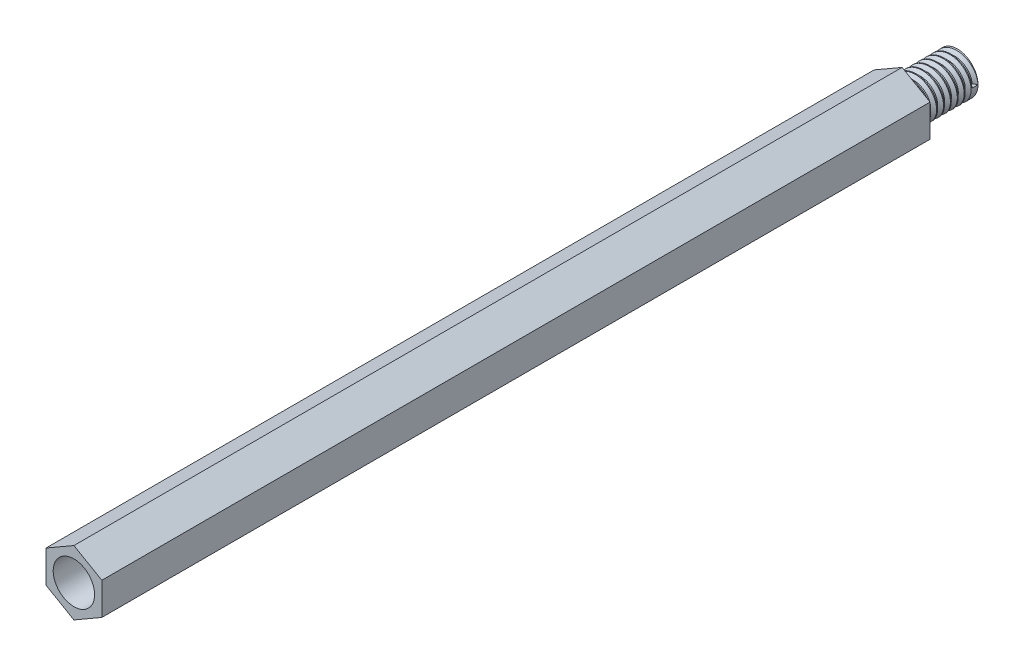
SolidWorks part; units mm, degrees
ref_plane "前视基准面" through (0, 0, 0) normal (0, 0, 1) x (1, 0, 0)
ref_plane "上视基准面" through (0, 0, 0) normal (0, 1, 0) x (1, 0, 0)
ref_plane "右视基准面" through (0, 0, 0) normal (1, 0, 0) x (0, 0, -1)
other "Configuration Table"
sketch "草图1" plane through (0, 0, 0) normal (0, 0, 1) x (1, 0, 0)
  circle A0 centre (0, 0) radius 1.5
  circle A1 centre (0, 0) radius 2.335
  dimension "D1" = 3
  dimension "D2" = 4.67
extrude "凸台-拉伸1" add sketch "草图1" along normal blind 60
sketch "草图3" plane through (0, 0, 0) normal (0, 0, 1) x (1, 0, 0)
  line L1 (0, 2.335) -> (-2.0222, 1.1675)
  line L2 (-2.0222, 1.1675) -> (-2.0222, -1.1675)
  line L3 (-2.0222, -1.1675) -> (0, -2.335)
  line L4 (0, -2.335) -> (2.0222, -1.1675)
  line L5 (2.0222, -1.1675) -> (2.0222, 1.1675)
  line L6 (2.0222, 1.1675) -> (0, 2.335)
  circle A0 centre (0, 0) radius 2.0222 construction
extrude "切除-拉伸2" cut sketch "草图3" along normal blind 60 flip side to cut
sketch "草图4" plane through (0, 0, 0) normal (0, 0, 1) x (1, 0, 0)
  circle A0 centre (0, 0) radius 1.5
sketch "草图5" plane through (0, 0, 0) normal (0, 0, 1) x (1, 0, 0)
  circle A0 centre (0, 0) radius 1.5
extrude "凸台-拉伸2" add sketch "草图5" against normal blind 4 separate body
thread "螺纹线1" pitch 0.5 method cut profile "螺纹线轮廓1" start angle 0, offset 0, length 4, pitch 0.5, diameter 3
ref_plane "基准面1" through (1.5, 0, -4) normal (0, -1, 0) x (1, 0, 0)
sketch "螺纹线轮廓1" plane through (1.5, 0, -4) normal (0, -1, 0) x (1, 0, 0)
  line L0 (0, 0) -> (0, 0.5) construction
  line L11 (0, 0) -> (0, 0.4375)
  line L12 (0, 0.4375) -> (-0.2706, 0.2812)
  line L13 (-0.2706, 0.2812) -> (-0.2706, 0.1562)
  line L15 (-0.2706, 0.1562) -> (0, 0)
  line L17 (-0.2706, 0.2187) -> (0, 0.2187) construction
  point P2 (0, 0)
  dimension "Pitch" = 0.5
  dimension "Profile_Angle" = 60
  dimension "Profile_Land" = 0.125
  dimension "Profile_Height" = 0.2706
